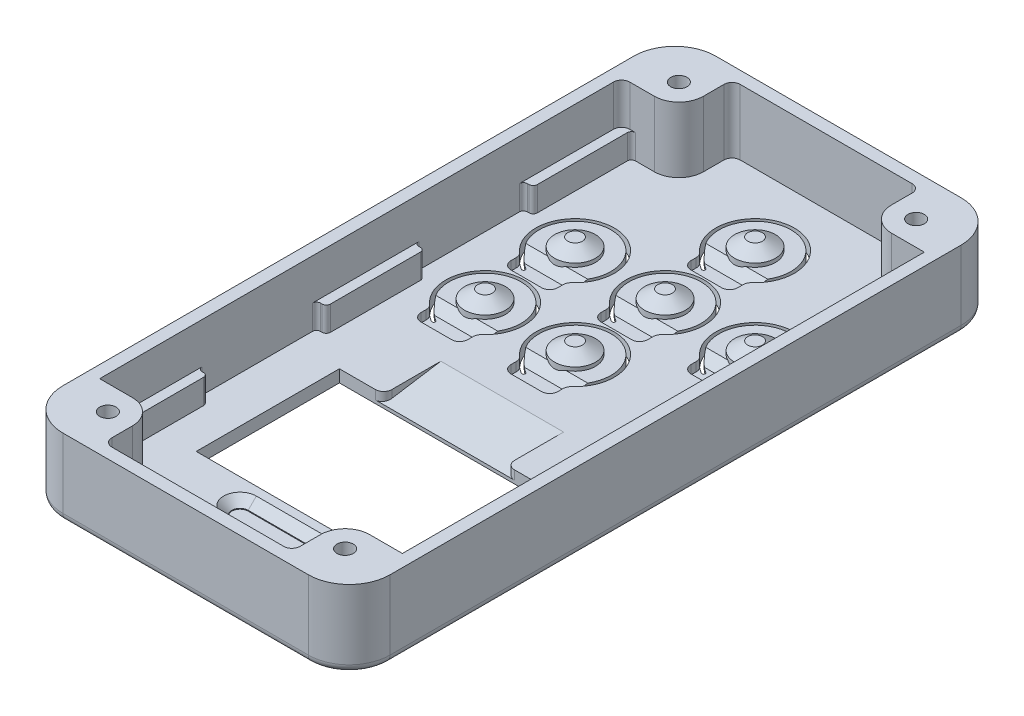
SolidWorks part; units mm, degrees
ref_plane "Front Plane" through (0, 0, 0) normal (0, 0, 1) x (1, 0, 0)
ref_plane "Top Plane" through (0, 0, 0) normal (0, 1, 0) x (1, 0, 0)
ref_plane "Right Plane" through (0, 0, 0) normal (1, 0, 0) x (0, 0, -1)
sketch "Base Sketch" plane through (0, 0, 0) normal (0, 1, 0) x (1, 0, 0)
  line L0 (0, 0) -> (40, 0)
  line L1 (40, 0) -> (40, 79.79)
  line L2 (40, 79.79) -> (0, 79.79)
  line L3 (0, 79.79) -> (0, 0)
extrude "Base" add sketch "Base Sketch" along normal blind 9.5
fillet "Corner Rounds R5" radius 5 4 edges at (0, 4.75, -79.79) (40, 4.75, -79.79) (40, 4.75, 0) (0, 4.75, 0)
shell "Shell 1.5" thickness 1.5 removed face at (20, 9.5, -39.895)
sketch "Boss Sketch" plane through (0, 0, 0) normal (0, 1, 0) x (1, 0, 0)
  line L0 (1.5, 1.5) -> (8.5, 1.5)
  line L1 (8.5, 1.5) -> (8.5, 5)
  line L2 (5.5, 8) -> (1.5, 8)
  line L3 (1.5, 8) -> (1.5, 1.5)
  line L4 (38.5, 1.5) -> (31.5, 1.5)
  line L5 (31.5, 1.5) -> (31.5, 5)
  line L6 (34.5, 8) -> (38.5, 8)
  line L7 (38.5, 8) -> (38.5, 1.5)
  line L16 (1.5, 78.29) -> (8.5, 78.29)
  line L17 (8.5, 78.29) -> (8.5, 74.79)
  line L18 (5.5, 71.79) -> (1.5, 71.79)
  line L19 (1.5, 71.79) -> (1.5, 78.29)
  line L20 (38.5, 78.29) -> (31.5, 78.29)
  line L21 (31.5, 78.29) -> (31.5, 74.79)
  line L22 (34.5, 71.79) -> (38.5, 71.79)
  line L23 (38.5, 71.79) -> (38.5, 78.29)
  arc A0 (8.5, 5) -> (5.5, 8) centre (5.4999, 4.9999) ccw
  circle A1 centre (5.5, 5) radius 1
  arc A2 (31.5, 5) -> (34.5, 8) centre (34.5001, 4.9999) cw
  circle A3 centre (34.5, 5) radius 1
  circle A5 centre (5.5, 74.79) radius 1
  circle A7 centre (34.5, 74.79) radius 1
  arc A8 (8.5, 74.79) -> (5.5, 71.79) centre (5.4999, 74.7901) cw
  arc A9 (31.5, 74.79) -> (34.5, 71.79) centre (34.5001, 74.7901) ccw
extrude "Corner Bosses + M2 Pilot Holes" add sketch "Boss Sketch" along normal blind 9.5
sketch "Ledge Sketch" plane through (0, 0, 0) normal (0, 1, 0) x (1, 0, 0)
  line L0 (1.5, 8) -> (2.7, 8)
  line L1 (2.7, 8) -> (2.7, 20)
  line L2 (2.7, 20) -> (1.5, 20)
  line L3 (1.5, 20) -> (1.5, 8)
  line L4 (37.3, 8) -> (38.5, 8)
  line L5 (38.5, 8) -> (38.5, 20)
  line L6 (38.5, 20) -> (37.3, 20)
  line L7 (37.3, 20) -> (37.3, 8)
  line L8 (1.5, 34.5) -> (2.7, 34.5)
  line L9 (2.7, 34.5) -> (2.7, 46.5)
  line L10 (2.7, 46.5) -> (1.5, 46.5)
  line L11 (1.5, 46.5) -> (1.5, 34.5)
  line L12 (37.3, 34.5) -> (38.5, 34.5)
  line L13 (38.5, 34.5) -> (38.5, 46.5)
  line L14 (38.5, 46.5) -> (37.3, 46.5)
  line L15 (37.3, 46.5) -> (37.3, 34.5)
  line L16 (1.5, 59.79) -> (2.7, 59.79)
  line L17 (2.7, 59.79) -> (2.7, 71.79)
  line L18 (2.7, 71.79) -> (1.5, 71.79)
  line L19 (1.5, 71.79) -> (1.5, 59.79)
  line L20 (37.3, 59.79) -> (38.5, 59.79)
  line L21 (38.5, 59.79) -> (38.5, 71.79)
  line L22 (38.5, 71.79) -> (37.3, 71.79)
  line L23 (37.3, 71.79) -> (37.3, 59.79)
extrude "Side Ledges" add sketch "Ledge Sketch" along normal blind 4.5
fillet "Outer Face Round R1" radius 1 8 edges at (1.4645, 0, -1.4645) (20, 0, 0) (38.5355, 0, -1.4645) (40, 0, -39.895) (38.5355, 0, -78.3255) (20, 0, -79.79) (1.4645, 0, -78.3255) (0, 0, -39.895)
sketch "Window Sketch" plane through (0, 0, 0) normal (0, 1, 0) x (1, 0, 0)
  line L0 (7.1, 14.5) -> (32.9, 14.5)
  line L1 (32.9, 14.5) -> (32.9, 31.7)
  line L2 (32.9, 31.7) -> (7.1, 31.7)
  line L3 (7.1, 31.7) -> (7.1, 14.5)
extrude "Display Window" cut sketch "Window Sketch" along normal through all
ref_plane "Mid Plane X20" through (20, 0, 0) normal (1, 0, 0) x (0, 0, -1)
sketch "Ramp Sketch" plane through (20, 0, 0) normal (1, 0, 0) x (0, 0, -1)
  line L0 (31, 0.4) -> (31.7, 0.4)
  line L1 (31.7, 0.4) -> (38.7, 1.5)
  line L2 (38.7, 1.5) -> (38.7, 2.5)
  line L3 (38.7, 2.5) -> (31, 2.5)
  line L4 (31, 2.5) -> (31, 0.4)
extrude "Cable Ramp" cut sketch "Ramp Sketch" against normal blind 7.5 and the other way blind 7.5
ref_plane "Plate Inner Face" through (0, 1.5, 0) normal (0, 1, 0) x (1, 0, 0)
sketch "LED Window Sketch" plane through (0, 1.5, 0) normal (0, 1, 0) x (1, 0, 0)
  circle A0 centre (20, 7.28) radius 1.7
  dimension "D1" = 3.4
extrude "LED Window" cut sketch "LED Window Sketch" against normal blind 1.1
sketch "Plunger Stems Sketch" plane through (0, 1.5, 0) normal (0, 1, 0) x (1, 0, 0)
  circle A0 centre (9, 47.6) radius 2.5
  circle A1 centre (20, 47.6) radius 2.5
  circle A2 centre (9, 58.6) radius 2.5
  circle A3 centre (20, 58.6) radius 2.5
  circle A4 centre (31, 58.6) radius 2.5
  circle A5 centre (20, 69.6) radius 2.5
extrude "Plunger Stems 5.0" add sketch "Plunger Stems Sketch" along normal blind 0.45
ref_plane "Plunger Cone Base" through (0, 1.95, 0) normal (0, 1, 0) x (1, 0, 0)
sketch "Plunger Cone Sketch" plane through (0, 1.95, 0) normal (0, 1, 0) x (1, 0, 0)
  circle A0 centre (9, 47.6) radius 2.5
  circle A1 centre (20, 47.6) radius 2.5
  circle A2 centre (9, 58.6) radius 2.5
  circle A3 centre (20, 58.6) radius 2.5
  circle A4 centre (31, 58.6) radius 2.5
  circle A5 centre (20, 69.6) radius 2.5
extrude "Plunger Cones to 1.8" add sketch "Plunger Cone Sketch" along normal blind 1 draft 57.995
fillet "Boss Junction Fillets R1" radius 1 8 edges at (1.5, 7, -71.79) (37.3, 3, -71.79) (37.3, 3, -8) (2.7, 3, -8) (31.5, 5.5, -78.29) (8.5, 5.5, -78.29) (31.5, 5.5, -1.5) (8.5, 5.5, -1.5)
sketch "C-Slot Sketch" plane through (0, 0, 0) normal (0, 1, 0) x (1, 0, 0)
  arc A0 (10.4434, 43.0222) -> (7.5566, 43.0222) centre (9, 47.6) ccw
  arc A1 (7.5566, 43.0222) -> (7.6769, 43.4036) centre (7.6168, 43.2129) ccw
  arc A2 (7.6769, 43.4036) -> (10.3231, 43.4036) centre (9, 47.6) cw
  arc A3 (10.3231, 43.4036) -> (10.4434, 43.0222) centre (10.3832, 43.2129) ccw
  arc A4 (21.4434, 43.0222) -> (18.5566, 43.0222) centre (20, 47.6) ccw
  arc A5 (18.5566, 43.0222) -> (18.6769, 43.4036) centre (18.6168, 43.2129) ccw
  arc A6 (18.6769, 43.4036) -> (21.3231, 43.4036) centre (20, 47.6) cw
  arc A7 (21.3231, 43.4036) -> (21.4434, 43.0222) centre (21.3832, 43.2129) ccw
  arc A8 (10.4434, 54.0222) -> (7.5566, 54.0222) centre (9, 58.6) ccw
  arc A9 (7.5566, 54.0222) -> (7.6769, 54.4036) centre (7.6168, 54.2129) ccw
  arc A10 (7.6769, 54.4036) -> (10.3231, 54.4036) centre (9, 58.6) cw
  arc A11 (10.3231, 54.4036) -> (10.4434, 54.0222) centre (10.3832, 54.2129) ccw
  arc A12 (21.4434, 54.0222) -> (18.5566, 54.0222) centre (20, 58.6) ccw
  arc A13 (18.5566, 54.0222) -> (18.6769, 54.4036) centre (18.6168, 54.2129) ccw
  arc A14 (18.6769, 54.4036) -> (21.3231, 54.4036) centre (20, 58.6) cw
  arc A15 (21.3231, 54.4036) -> (21.4434, 54.0222) centre (21.3832, 54.2129) ccw
  arc A16 (32.4434, 54.0222) -> (29.5566, 54.0222) centre (31, 58.6) ccw
  arc A17 (29.5566, 54.0222) -> (29.6769, 54.4036) centre (29.6168, 54.2129) ccw
  arc A18 (29.6769, 54.4036) -> (32.3231, 54.4036) centre (31, 58.6) cw
  arc A19 (32.3231, 54.4036) -> (32.4434, 54.0222) centre (32.3832, 54.2129) ccw
  arc A20 (21.4434, 65.0222) -> (18.5566, 65.0222) centre (20, 69.6) ccw
  arc A21 (18.5566, 65.0222) -> (18.6769, 65.4036) centre (18.6168, 65.2129) ccw
  arc A22 (18.6769, 65.4036) -> (21.3231, 65.4036) centre (20, 69.6) cw
  arc A23 (21.3231, 65.4036) -> (21.4434, 65.0222) centre (21.3832, 65.2129) ccw
sketch "Sketch10" plane through (0, 1.5, 0) normal (0, 1, 0) x (1, 0, 0)
  line L0 (11.864, 44.259) -> (11.864, 41.636)
  line L1 (11.864, 41.636) -> (6.136, 41.636)
  line L2 (6.136, 41.636) -> (6.136, 44.259)
  line L3 (6.136, 44.259) -> (11.864, 44.259)
  line L4 (22.864, 44.259) -> (22.864, 41.636)
  line L5 (22.864, 41.636) -> (17.136, 41.636)
  line L6 (17.136, 41.636) -> (17.136, 44.259)
  line L7 (17.136, 44.259) -> (22.864, 44.259)
  line L8 (11.864, 55.259) -> (11.864, 52.636)
  line L9 (11.864, 52.636) -> (6.136, 52.636)
  line L10 (6.136, 52.636) -> (6.136, 55.259)
  line L11 (6.136, 55.259) -> (11.864, 55.259)
  line L12 (22.864, 55.259) -> (22.864, 52.636)
  line L13 (22.864, 52.636) -> (17.136, 52.636)
  line L14 (17.136, 52.636) -> (17.136, 55.259)
  line L15 (17.136, 55.259) -> (22.864, 55.259)
  line L16 (33.864, 55.259) -> (33.864, 52.636)
  line L17 (33.864, 52.636) -> (28.136, 52.636)
  line L18 (28.136, 52.636) -> (28.136, 55.259)
  line L19 (28.136, 55.259) -> (33.864, 55.259)
  line L20 (22.864, 66.259) -> (22.864, 63.636)
  line L21 (22.864, 63.636) -> (17.136, 63.636)
  line L22 (17.136, 63.636) -> (17.136, 66.259)
  line L23 (17.136, 66.259) -> (22.864, 66.259)
extrude "Cut-Extrude7" cut sketch "Sketch10" against normal blind 1.1
sketch "Sketch11" plane through (0, 0, 0) normal (0, 1, 0) x (1, 0, 0)
  arc A0 (11.4, 43.4431) -> (6.6, 43.4431) centre (9, 47.6) ccw
  arc A1 (6.6, 43.4431) -> (6.8, 43.7895) centre (6.7, 43.6163) ccw
  arc A2 (6.8, 43.7895) -> (11.2, 43.7895) centre (9, 47.6) cw
  arc A3 (11.2, 43.7895) -> (11.4, 43.4431) centre (11.3, 43.6163) ccw
  arc A4 (22.4, 43.4431) -> (17.6, 43.4431) centre (20, 47.6) ccw
  arc A5 (17.6, 43.4431) -> (17.8, 43.7895) centre (17.7, 43.6163) ccw
  arc A6 (17.8, 43.7895) -> (22.2, 43.7895) centre (20, 47.6) cw
  arc A7 (22.2, 43.7895) -> (22.4, 43.4431) centre (22.3, 43.6163) ccw
  arc A8 (11.4, 54.4431) -> (6.6, 54.4431) centre (9, 58.6) ccw
  arc A9 (6.6, 54.4431) -> (6.8, 54.7895) centre (6.7, 54.6163) ccw
  arc A10 (6.8, 54.7895) -> (11.2, 54.7895) centre (9, 58.6) cw
  arc A11 (11.2, 54.7895) -> (11.4, 54.4431) centre (11.3, 54.6163) ccw
  arc A12 (22.4, 54.4431) -> (17.6, 54.4431) centre (20, 58.6) ccw
  arc A13 (17.6, 54.4431) -> (17.8, 54.7895) centre (17.7, 54.6163) ccw
  arc A14 (17.8, 54.7895) -> (22.2, 54.7895) centre (20, 58.6) cw
  arc A15 (22.2, 54.7895) -> (22.4, 54.4431) centre (22.3, 54.6163) ccw
  arc A16 (33.4, 54.4431) -> (28.6, 54.4431) centre (31, 58.6) ccw
  arc A17 (28.6, 54.4431) -> (28.8, 54.7895) centre (28.7, 54.6163) ccw
  arc A18 (28.8, 54.7895) -> (33.2, 54.7895) centre (31, 58.6) cw
  arc A19 (33.2, 54.7895) -> (33.4, 54.4431) centre (33.3, 54.6163) ccw
  arc A20 (22.4, 65.4431) -> (17.6, 65.4431) centre (20, 69.6) ccw
  arc A21 (17.6, 65.4431) -> (17.8, 65.7895) centre (17.7, 65.6163) ccw
  arc A22 (17.8, 65.7895) -> (22.2, 65.7895) centre (20, 69.6) cw
  arc A23 (22.2, 65.7895) -> (22.4, 65.4431) centre (22.3, 65.6163) ccw
extrude "Button C-Slots 300deg 0.4" cut sketch "Sketch11" along normal through all
chamfer "Chamfer1" distance 1.1 angle 45 6 edges at (9, 1.5, -44.259) (20, 1.5, -66.259) (31, 1.5, -55.259) (20, 1.5, -55.259) (9, 1.5, -55.259) (20, 1.5, -44.259)
fillet "Fillet1" radius 1 24 edges at (11.864, 0.95, -43.7481) (11.864, 0.95, -41.636) (6.136, 0.95, -41.636) (6.136, 0.95, -43.7481) (22.864, 0.95, -63.636) (22.864, 0.95, -65.7481) (17.136, 0.95, -63.636) (17.136, 0.95, -65.7481) (33.864, 0.95, -52.636) (33.864, 0.95, -54.7481) (28.136, 0.95, -52.636) (28.136, 0.95, -54.7481) (22.864, 0.95, -52.636) (22.864, 0.95, -54.7481) (17.136, 0.95, -52.636) (17.136, 0.95, -54.7481) (11.864, 0.95, -52.636) (11.864, 0.95, -54.7481) (6.136, 0.95, -52.636) (6.136, 0.95, -54.7481) (22.864, 0.95, -41.636) (22.864, 0.95, -43.7481) (17.136, 0.95, -41.636) (17.136, 0.95, -43.7481)
fillet "Fillet2" radius 0.5 17 edges at (2.7, 3, -71.79) (1.5, 3, -59.79) (2.7, 3, -59.79) (38.5, 3, -59.79) (37.3, 3, -59.79) (38.5, 3, -46.5) (37.3, 3, -46.5) (2.7, 3, -46.5) (1.5, 3, -46.5) (38.5, 3, -34.5) (37.3, 3, -34.5) (2.7, 3, -34.5) (1.5, 3, -34.5) (38.5, 3, -20) (37.3, 3, -20) (2.7, 3, -20) (1.5, 3, -20)
fillet "Fillet3" radius 1 2 edges at (27.5, 0.95, -31.7) (12.5, 0.95, -31.7)
sketch "Button Symbols Cut Sketch" plane through (0, 0, 0) normal (0, 1, 0) x (1, 0, 0)
  line L0 (7.0908, 45.6908) -> (7.7272, 46.3272)
  line L1 (10.2728, 46.3272) -> (10.9092, 45.6908)
  line L2 (8.55, 47.2) -> (9.45, 47.2)
  line L3 (9.45, 47.2) -> (9.45, 44.4)
  line L4 (9.45, 44.4) -> (8.55, 44.4)
  line L5 (8.55, 44.4) -> (8.55, 47.2)
  line L6 (20, 44.8) -> (22.4249, 49)
  line L7 (22.4249, 49) -> (17.5751, 49)
  line L8 (17.5751, 49) -> (20, 44.8)
  line L9 (6.2, 58.6) -> (10.4, 56.1751)
  line L10 (10.4, 56.1751) -> (10.4, 61.0249)
  line L11 (10.4, 61.0249) -> (6.2, 58.6)
  line L12 (33.8, 58.6) -> (29.6, 61.0249)
  line L13 (29.6, 61.0249) -> (29.6, 56.1751)
  line L14 (29.6, 56.1751) -> (33.8, 58.6)
  line L15 (20, 72.4) -> (17.5751, 68.2)
  line L16 (17.5751, 68.2) -> (22.4249, 68.2)
  line L17 (22.4249, 68.2) -> (20, 72.4)
  arc A0 (10.9092, 45.6908) -> (7.0908, 45.6908) centre (9, 47.6) ccw
  arc A1 (7.7272, 46.3272) -> (10.2728, 46.3272) centre (9, 47.6) cw
  circle A2 centre (20, 58.6) radius 2.4
  circle A3 centre (20, 58.6) radius 1.5
sketch "Button Symbols Inlay Sketch" plane through (0, 0, 0) normal (0, 1, 0) x (1, 0, 0)
  line L0 (7.0908, 45.6908) -> (7.7272, 46.3272)
  line L1 (10.2728, 46.3272) -> (10.9092, 45.6908)
  line L2 (8.55, 47.2) -> (9.45, 47.2)
  line L3 (9.45, 47.2) -> (9.45, 44.4)
  line L4 (9.45, 44.4) -> (8.55, 44.4)
  line L5 (8.55, 44.4) -> (8.55, 47.2)
  line L6 (20, 44.8) -> (22.4249, 49)
  line L7 (22.4249, 49) -> (17.5751, 49)
  line L8 (17.5751, 49) -> (20, 44.8)
  line L9 (6.2, 58.6) -> (10.4, 56.1751)
  line L10 (10.4, 56.1751) -> (10.4, 61.0249)
  line L11 (10.4, 61.0249) -> (6.2, 58.6)
  line L12 (33.8, 58.6) -> (29.6, 61.0249)
  line L13 (29.6, 61.0249) -> (29.6, 56.1751)
  line L14 (29.6, 56.1751) -> (33.8, 58.6)
  line L15 (20, 72.4) -> (17.5751, 68.2)
  line L16 (17.5751, 68.2) -> (22.4249, 68.2)
  line L17 (22.4249, 68.2) -> (20, 72.4)
  arc A0 (10.9092, 45.6908) -> (7.0908, 45.6908) centre (9, 47.6) ccw
  arc A1 (7.7272, 46.3272) -> (10.2728, 46.3272) centre (9, 47.6) cw
  circle A2 centre (20, 58.6) radius 2.4
  circle A3 centre (20, 58.6) radius 1.5
sketch "Sketch14" plane through (0, 0, 0) normal (0, 1, 0) x (1, 0, 0)
  line L0 (8.4, 47) -> (8.4, 45.2)
  line L1 (9.6, 45.2) -> (9.6, 47)
  line L2 (20.5196, 44.9) -> (22.7713, 48.8)
  line L3 (22.2517, 49.7) -> (17.7483, 49.7)
  line L4 (17.2287, 48.8) -> (19.4804, 44.9)
  line L5 (6.1, 58.0804) -> (10, 55.8287)
  line L6 (10.9, 56.3483) -> (10.9, 60.8517)
  line L7 (10, 61.3713) -> (6.1, 59.1196)
  line L8 (33.9, 59.1196) -> (30, 61.3713)
  line L9 (29.1, 60.8517) -> (29.1, 56.3483)
  line L10 (30, 55.8287) -> (33.9, 58.0804)
  line L11 (19.4804, 72.5) -> (17.2287, 68.6)
  line L12 (17.7483, 67.7) -> (22.2517, 67.7)
  line L13 (22.7713, 68.6) -> (20.5196, 72.5)
  arc A0 (11.4513, 45.5431) -> (6.5487, 45.5431) centre (9, 47.6) ccw
  arc A1 (6.5487, 45.5431) -> (7.4679, 46.3144) centre (7.0083, 45.9288) ccw
  arc A2 (7.4679, 46.3144) -> (10.5321, 46.3144) centre (9, 47.6) cw
  arc A3 (10.5321, 46.3144) -> (11.4513, 45.5431) centre (10.9917, 45.9288) ccw
  arc A4 (8.4, 45.2) -> (9.6, 45.2) centre (9, 45.2) ccw
  arc A5 (9.6, 47) -> (8.4, 47) centre (9, 47) ccw
  arc A6 (19.4804, 44.9) -> (20.5196, 44.9) centre (20, 45.2) ccw
  arc A7 (22.7713, 48.8) -> (22.2517, 49.7) centre (22.2517, 49.1) ccw
  arc A8 (17.7483, 49.7) -> (17.2287, 48.8) centre (17.7483, 49.1) ccw
  arc A9 (6.1, 59.1196) -> (6.1, 58.0804) centre (6.4, 58.6) ccw
  arc A10 (10, 55.8287) -> (10.9, 56.3483) centre (10.3, 56.3483) ccw
  arc A11 (10.9, 60.8517) -> (10, 61.3713) centre (10.3, 60.8517) ccw
  circle A12 centre (20, 58.6) radius 3.1
  circle A13 centre (20, 58.6) radius 1.9
  arc A14 (33.9, 58.0804) -> (33.9, 59.1196) centre (33.6, 58.6) ccw
  arc A15 (30, 61.3713) -> (29.1, 60.8517) centre (29.7, 60.8517) ccw
  arc A16 (29.1, 56.3483) -> (30, 55.8287) centre (29.7, 56.3483) ccw
  arc A17 (20.5196, 72.5) -> (19.4804, 72.5) centre (20, 72.2) ccw
  arc A18 (17.2287, 68.6) -> (17.7483, 67.7) centre (17.7483, 68.3) ccw
  arc A19 (22.2517, 67.7) -> (22.7713, 68.6) centre (22.2517, 68.3) ccw
extrude "Button Symbol Recess 0.4" cut sketch "Sketch14" along normal blind 0.4
sketch "Sketch15" plane through (0, 0, 0) normal (0, 1, 0) x (1, 0, 0)
  line L0 (8.4, 47) -> (8.4, 45.2)
  line L1 (9.6, 45.2) -> (9.6, 47)
  line L2 (20.5196, 44.9) -> (22.7713, 48.8)
  line L3 (22.2517, 49.7) -> (17.7483, 49.7)
  line L4 (17.2287, 48.8) -> (19.4804, 44.9)
  line L5 (6.1, 58.0804) -> (10, 55.8287)
  line L6 (10.9, 56.3483) -> (10.9, 60.8517)
  line L7 (10, 61.3713) -> (6.1, 59.1196)
  line L8 (33.9, 59.1196) -> (30, 61.3713)
  line L9 (29.1, 60.8517) -> (29.1, 56.3483)
  line L10 (30, 55.8287) -> (33.9, 58.0804)
  line L11 (19.4804, 72.5) -> (17.2287, 68.6)
  line L12 (17.7483, 67.7) -> (22.2517, 67.7)
  line L13 (22.7713, 68.6) -> (20.5196, 72.5)
  arc A0 (11.4513, 45.5431) -> (6.5487, 45.5431) centre (9, 47.6) ccw
  arc A1 (6.5487, 45.5431) -> (7.4679, 46.3144) centre (7.0083, 45.9288) ccw
  arc A2 (7.4679, 46.3144) -> (10.5321, 46.3144) centre (9, 47.6) cw
  arc A3 (10.5321, 46.3144) -> (11.4513, 45.5431) centre (10.9917, 45.9288) ccw
  arc A4 (8.4, 45.2) -> (9.6, 45.2) centre (9, 45.2) ccw
  arc A5 (9.6, 47) -> (8.4, 47) centre (9, 47) ccw
  arc A6 (19.4804, 44.9) -> (20.5196, 44.9) centre (20, 45.2) ccw
  arc A7 (22.7713, 48.8) -> (22.2517, 49.7) centre (22.2517, 49.1) ccw
  arc A8 (17.7483, 49.7) -> (17.2287, 48.8) centre (17.7483, 49.1) ccw
  arc A9 (6.1, 59.1196) -> (6.1, 58.0804) centre (6.4, 58.6) ccw
  arc A10 (10, 55.8287) -> (10.9, 56.3483) centre (10.3, 56.3483) ccw
  arc A11 (10.9, 60.8517) -> (10, 61.3713) centre (10.3, 60.8517) ccw
  circle A12 centre (20, 58.6) radius 3.1
  circle A13 centre (20, 58.6) radius 1.9
  arc A14 (33.9, 58.0804) -> (33.9, 59.1196) centre (33.6, 58.6) ccw
  arc A15 (30, 61.3713) -> (29.1, 60.8517) centre (29.7, 60.8517) ccw
  arc A16 (29.1, 56.3483) -> (30, 55.8287) centre (29.7, 56.3483) ccw
  arc A17 (20.5196, 72.5) -> (19.4804, 72.5) centre (20, 72.2) ccw
  arc A18 (17.2287, 68.6) -> (17.7483, 67.7) centre (17.7483, 68.3) ccw
  arc A19 (22.2517, 67.7) -> (22.7713, 68.6) centre (22.2517, 68.3) ccw
extrude "Button Symbol Inlays 0.4 (colour 2)" add sketch "Sketch15" along normal blind 0.4 separate body
sketch "I2C Header Pocket Sketch" plane through (0, 1.5, 0) normal (0, 1, 0) x (1, 0, 0)
  line L0 (15.5, 9.4) -> (24.5, 9.4)
  line L1 (25.5, 10.4) -> (25.5, 11.9)
  line L2 (24.5, 12.9) -> (15.5, 12.9)
  line L3 (14.5, 11.9) -> (14.5, 10.4)
  line L4 (32.9, 14.5) -> (7.1, 14.5) construction
  arc A0 (24.5, 9.4) -> (25.5, 10.4) centre (24.5, 10.4) ccw
  arc A1 (25.5, 11.9) -> (24.5, 12.9) centre (24.5, 11.9) ccw
  arc A2 (15.5, 12.9) -> (14.5, 11.9) centre (15.5, 11.9) ccw
  arc A3 (14.5, 10.4) -> (15.5, 9.4) centre (15.5, 10.4) ccw
  dimension "D3" = 1
  dimension "D1" = 1.6
  dimension "D2" = 11
  dimension "D4" = 2.6
sketch "Sketch17" plane through (0, 1.5, 0) normal (0, 1, 0) x (1, 0, 0)
  line L0 (15.2, 10.45) -> (24.8, 10.45)
  line L1 (24.8, 11.85) -> (15.2, 11.85)
  arc A0 (24.8, 10.45) -> (24.8, 11.85) centre (24.8, 11.15) ccw
  arc A1 (15.2, 11.85) -> (15.2, 10.45) centre (15.2, 11.15) ccw
sketch "Sketch18" plane through (0, 0, -14.5) normal (0, 0, -1) x (-1, 0, 0)
  line L4 (-32.9, 1.5) -> (-32.9, 0)
  line L5 (-32.9, 0) -> (-7.1, 0)
  line L6 (-7.1, 0) -> (-7.1, 1.5)
  line L7 (-7.1, 1.5) -> (-32.9, 1.5)
  line L8 (-32.9, 1.5) -> (-32.9, 0)
  line L9 (-32.9, 0) -> (-7.1, 0)
  line L10 (-7.1, 0) -> (-7.1, 1.5)
  line L11 (-7.1, 1.5) -> (-32.9, 1.5)
  dimension "D1" = 0
extrude "Cut-Extrude16" cut sketch "Sketch18" against normal blind 0.3
sketch "Sketch19" plane through (0, 1.5, 0) normal (0, 1, 0) x (1, 0, 0)
  line L0 (15.2999, 10.35) -> (24.7001, 10.35)
  line L1 (25.5, 11.1499) -> (25.5, 11.1501)
  line L2 (24.7001, 11.95) -> (15.2999, 11.95)
  line L3 (14.5, 11.1501) -> (14.5, 11.1499)
  arc A0 (24.7001, 10.35) -> (25.5, 11.1499) centre (24.7001, 11.1499) ccw
  arc A1 (25.5, 11.1501) -> (24.7001, 11.95) centre (24.7001, 11.1501) ccw
  arc A2 (15.2999, 11.95) -> (14.5, 11.1501) centre (15.2999, 11.1501) ccw
  arc A3 (14.5, 11.1499) -> (15.2999, 10.35) centre (15.2999, 11.1499) ccw
sketch "Sketch20" plane through (0, 1.5, 0) normal (0, 1, 0) x (1, 0, 0)
  line L0 (15.5, 10.15) -> (24.5, 10.15)
  line L1 (24.5, 12.15) -> (15.5, 12.15)
  arc A0 (24.5, 10.15) -> (24.5, 12.15) centre (24.5, 11.15) ccw
  arc A1 (15.5, 12.15) -> (15.5, 10.15) centre (15.5, 11.15) ccw
extrude "I2C Header Lead Pocket 2.0 (0.2 skin)" cut sketch "Sketch20" against normal blind 1.1
chamfer "Chamfer3" distance 1 angle 45 4 edges at (20, 1.5, -12.15) (14.5, 1.5, -11.15) (25.5, 1.5, -11.15) (20, 1.5, -10.15)
sketch "Sketch21" plane through (0, 0, 0) normal (0, -1, 0) x (1, 0, 0)
  circle A0 centre (20, -7.28) radius 2.5
  circle A1 centre (20, -7.28) radius 1.7
  circle A2 centre (20, -7.28) radius 1.7 construction
  circle A3 centre (20, -7.28) radius 2.6
  dimension "D2" = 5
  dimension "D3" = 0.1
  dimension "D1" = 0
extrude "Cut-Extrude17" cut sketch "Sketch21" against normal blind 0.1
